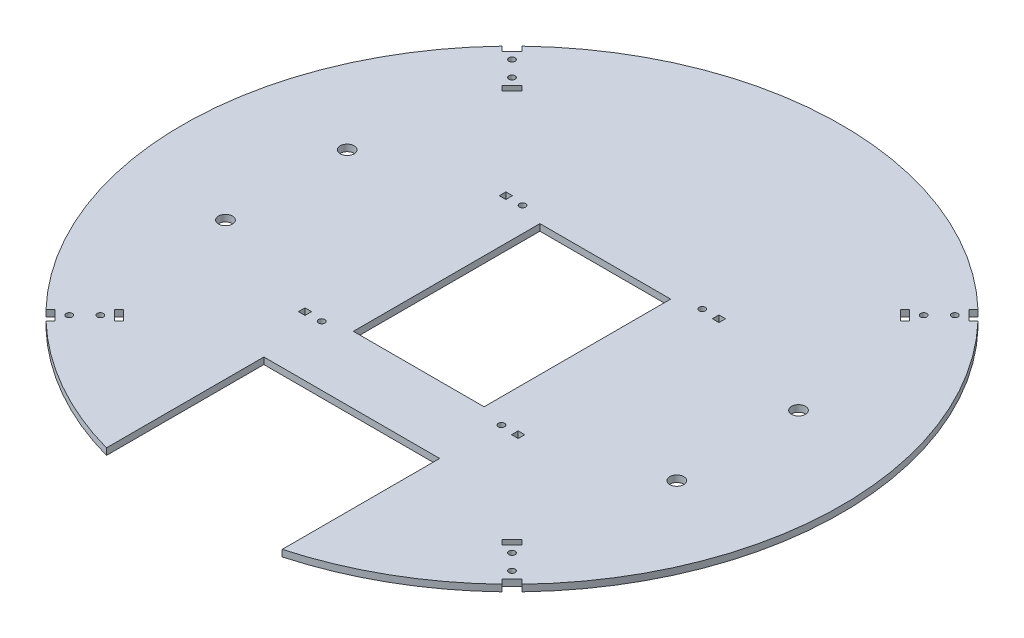
SolidWorks part; units mm, degrees
material "Acrylic (Medium-high impact)"
ref_plane "Front Plane" through (0, 0, 0) normal (0, 0, 1) x (1, 0, 0)
ref_plane "Top Plane" through (0, 0, 0) normal (0, 1, 0) x (1, 0, 0)
ref_plane "Right Plane" through (0, 0, 0) normal (1, 0, 0) x (0, 0, -1)
sketch "Sketch1" plane through (0, 0, 0) normal (0, 1, 0) x (1, 0, 0)
  line L0 (-29.75, -42.45) -> (-29.75, 42.45)
  line L1 (-31.75, -44.45) -> (31.75, -44.45) construction
  line L2 (-31.75, -44.45) -> (-31.75, 44.45) construction
  line L3 (-31.75, 44.45) -> (31.75, 44.45) construction
  line L4 (31.75, -44.45) -> (31.75, 44.45) construction
  line L5 (-31.75, -44.45) -> (31.75, 44.45) construction
  line L6 (-31.75, 44.45) -> (31.75, -44.45) construction
  line L7 (-29.75, 42.45) -> (29.75, 42.45)
  line L8 (29.75, -42.45) -> (29.75, 42.45)
  line L9 (-29.75, -42.45) -> (29.75, -42.45)
  circle A0 centre (0, 0) radius 150
  point P0 (0, 0)
  dimension "D3" = 300
  dimension "D1" = 63.5
  dimension "D2" = 88.9
  dimension "D4" = 2
extrude "Boss-Extrude1" add sketch "Sketch1" along normal blind 3
sketch "Sketch3" plane through (0, 3, 0) normal (0, 1, 0) x (1, 0, 0)
  line L0 (-42.4, 47.2) -> (-39.4, 44.2) construction
  line L1 (42.4, 47.2) -> (39.4, 44.2) construction
  line L2 (0, 0) -> (25.2091, 0) construction
  line L7 (-50, 44.2) -> (-47, 44.2)
  line L8 (-47, 44.2) -> (-47, 47.2)
  line L9 (-47, 47.2) -> (-50, 47.2)
  line L10 (-50, 47.2) -> (-50, 44.2)
  line L11 (-50, 44.2) -> (-47, 44.2)
  line L12 (-47, 44.2) -> (-47, 47.2)
  line L13 (-47, 47.2) -> (-50, 47.2)
  line L14 (-50, 47.2) -> (-50, 44.2)
  line L15 (47, 44.2) -> (50, 44.2)
  line L16 (50, 44.2) -> (50, 47.2)
  line L17 (50, 47.2) -> (47, 47.2)
  line L18 (47, 47.2) -> (47, 44.2)
  line L19 (47, 44.2) -> (50, 44.2)
  line L20 (50, 44.2) -> (50, 47.2)
  line L21 (50, 47.2) -> (47, 47.2)
  line L22 (47, 47.2) -> (47, 44.2)
  line L23 (47, -47.2) -> (50, -47.2) construction
  line L24 (50, -47.2) -> (50, -44.2) construction
  line L25 (50, -44.2) -> (47, -44.2) construction
  line L26 (47, -44.2) -> (47, -47.2) construction
  line L31 (-50, -47.2) -> (-47, -47.2) construction
  line L32 (-47, -47.2) -> (-47, -44.2) construction
  line L33 (-47, -44.2) -> (-50, -44.2) construction
  line L34 (-50, -44.2) -> (-50, -47.2) construction
  line L51 (47, -47.2) -> (50, -47.2)
  line L52 (50, -47.2) -> (50, -44.2)
  line L53 (50, -44.2) -> (47, -44.2)
  line L54 (47, -44.2) -> (47, -47.2)
  line L55 (-50, -47.2) -> (-47, -47.2)
  line L56 (-47, -47.2) -> (-47, -44.2)
  line L57 (-47, -44.2) -> (-50, -44.2)
  line L58 (-50, -44.2) -> (-50, -47.2)
  line L59 (0, 0) -> (0, -93.4335) construction
  circle A0 centre (-40.9, 45.7) radius 1.4224
  circle A1 centre (40.9, 45.7) radius 1.4224
  circle A2 centre (40.9, -45.7) radius 1.4224
  circle A3 centre (-40.9, -45.7) radius 1.4224
  circle A4 centre (-102.7, 27.7) radius 3.175
  circle A5 centre (-102.7, -27.7) radius 3.175
  circle A6 centre (102.7, 27.7) radius 3.175
  circle A7 centre (102.7, -27.7) radius 3.175
  dimension "D1" = 2.8448
  dimension "D4" = 6.35
  dimension "D2" = 0
  dimension "D3" = 0
extrude "Cut-Extrude1" cut sketch "Sketch3" against normal blind 10
sketch "Sketch4" plane through (0, 3, 0) normal (0, 1, 0) x (1, 0, 0)
  line L1 (-52.6396, -60.6627) -> (52.6396, -60.6627)
  line L2 (-52.6396, -60.6627) -> (-52.6396, 60.6627)
  line L3 (-52.6396, 60.6627) -> (52.6396, 60.6627)
  line L4 (52.6396, -60.6627) -> (52.6396, 60.6627)
  line L5 (-52.6396, -60.6627) -> (52.6396, 60.6627) construction
  line L6 (-52.6396, 60.6627) -> (52.6396, -60.6627) construction
  line L7 (-176.3133, 139.7199) -> (176.3133, 139.7199)
  line L8 (-176.3133, 139.7199) -> (-176.3133, -139.7199)
  line L9 (-176.3133, -139.7199) -> (176.3133, -139.7199)
  line L10 (176.3133, 139.7199) -> (176.3133, -139.7199)
  line L11 (-176.3133, 139.7199) -> (176.3133, -139.7199) construction
  line L12 (-176.3133, -139.7199) -> (176.3133, 139.7199) construction
  point P0 (0, 0)
  point P6 (0, 0)
extrude "Cut-Extrude2" [suppressed] cut sketch "Sketch4" against normal blind 10
sketch "Sketch6" plane through (0, 3, 0) normal (0, 1, 0) x (1, 0, 0)
  line L0 (-29.75, -42.45) -> (29.75, -42.45) construction
  line L1 (-40, -72.93) -> (40, -72.93)
  line L2 (-40, -72.93) -> (-40, -161.3295)
  line L3 (-40, -161.3295) -> (40, -161.3295)
  line L4 (40, -72.93) -> (40, -161.3295)
  line L5 (-40, -72.93) -> (40, -161.3295) construction
  line L6 (-40, -161.3295) -> (40, -72.93) construction
  point P0 (0, -117.1298)
  point P5 (0, 0)
  dimension "D1" = 30.48
  dimension "D2" = 80
extrude "Cut-Extrude3" cut sketch "Sketch6" against normal blind 3
sketch "Sketch7" plane through (0, 3, 0) normal (0, 1, 0) x (1, 0, 0)
  line L0 (0, 0) -> (0, 150) construction
  line L1 (0, 0) -> (-106.066, 106.066) construction
  line L2 (0, 0) -> (106.066, 106.066) construction
  line L3 (0, 0) -> (106.066, -106.066)
  line L4 (0, 0) -> (-106.066, -106.066) construction
  circle A0 centre (0, 0) radius 150 construction
  point P13 (0, 0)
  dimension "D1" = 45
  dimension "D2" = 4
ref_axis "Axis1" through (0, 3, 0) along (0, -1, 0)
ref_plane "Plane1" through (0, 0, 0) normal (0.7071, 0, 0.7071) x (0, -1, 0)
sketch "Sketch8" plane through (0, 0, 0) normal (0, -1, 0) x (1, 0, 0)
  line L0 (99.5234, 104.0136) -> (102.002, 97.5119) construction
  line L1 (92.4524, 96.9425) -> (94.9309, 90.4408) construction
  line L2 (103.821, 108.3111) -> (108.3111, 103.821) construction
  line L3 (106.1898, 101.6996) -> (108.3111, 103.821) construction
  line L4 (101.6996, 106.1898) -> (103.821, 108.3111) construction
  line L5 (101.6996, 106.1898) -> (106.1898, 101.6996) construction
  line L6 (90.6334, 86.1433) -> (92.7547, 88.2646)
  line L7 (92.7547, 88.2646) -> (88.2646, 92.7547)
  line L8 (88.2646, 92.7547) -> (86.1433, 90.6334)
  line L9 (86.1433, 90.6334) -> (90.6334, 86.1433)
  line L10 (90.6334, 86.1433) -> (92.7547, 88.2646)
  line L11 (92.7547, 88.2646) -> (88.2646, 92.7547)
  line L12 (88.2646, 92.7547) -> (86.1433, 90.6334)
  line L13 (86.1433, 90.6334) -> (90.6334, 86.1433)
  line L14 (103.821, 108.3111) -> (108.3111, 103.821)
  line L15 (106.1898, 101.6996) -> (108.3111, 103.821)
  line L16 (101.6996, 106.1898) -> (103.821, 108.3111)
  line L17 (101.6996, 106.1898) -> (106.1898, 101.6996)
  line L18 (86.1433, -90.6334) -> (88.2646, -92.7547)
  line L19 (88.2646, -92.7547) -> (92.7547, -88.2646)
  line L20 (92.7547, -88.2646) -> (90.6334, -86.1433)
  line L21 (90.6334, -86.1433) -> (86.1433, -90.6334)
  line L22 (108.3111, -103.821) -> (103.821, -108.3111)
  line L23 (101.6996, -106.1898) -> (103.821, -108.3111)
  line L24 (106.1898, -101.6996) -> (108.3111, -103.821)
  line L25 (106.1898, -101.6996) -> (101.6996, -106.1898)
  line L26 (104.0136, -99.5234) -> (97.5119, -102.002) construction
  line L27 (96.9425, -92.4524) -> (90.4408, -94.9309) construction
  line L28 (-90.6334, -86.1433) -> (-92.7547, -88.2646)
  line L29 (-92.7547, -88.2646) -> (-88.2646, -92.7547)
  line L30 (-88.2646, -92.7547) -> (-86.1433, -90.6334)
  line L31 (-86.1433, -90.6334) -> (-90.6334, -86.1433)
  line L32 (-103.821, -108.3111) -> (-108.3111, -103.821)
  line L33 (-106.1898, -101.6996) -> (-108.3111, -103.821)
  line L34 (-101.6996, -106.1898) -> (-103.821, -108.3111)
  line L35 (-101.6996, -106.1898) -> (-106.1898, -101.6996)
  line L36 (-99.5234, -104.0136) -> (-102.002, -97.5119) construction
  line L37 (-92.4524, -96.9425) -> (-94.9309, -90.4408) construction
  line L38 (-86.1433, 90.6334) -> (-88.2646, 92.7547)
  line L39 (-88.2646, 92.7547) -> (-92.7547, 88.2646)
  line L40 (-92.7547, 88.2646) -> (-90.6334, 86.1433)
  line L41 (-90.6334, 86.1433) -> (-86.1433, 90.6334)
  line L42 (-108.3111, 103.821) -> (-103.821, 108.3111)
  line L43 (-101.6996, 106.1898) -> (-103.821, 108.3111)
  line L44 (-106.1898, 101.6996) -> (-108.3111, 103.821)
  line L45 (-106.1898, 101.6996) -> (-101.6996, 106.1898)
  line L46 (-104.0136, 99.5234) -> (-97.5119, 102.002) construction
  line L47 (-96.9425, 92.4524) -> (-90.4408, 94.9309) construction
  circle A0 centre (100.7627, 100.7627) radius 1.4224
  circle A1 centre (93.6916, 93.6916) radius 1.4224
  circle A2 centre (100.7627, -100.7627) radius 1.4224
  circle A3 centre (93.6916, -93.6916) radius 1.4224
  circle A4 centre (-100.7627, -100.7627) radius 1.4224
  circle A5 centre (-93.6916, -93.6916) radius 1.4224
  circle A6 centre (-100.7627, 100.7627) radius 1.4224
  circle A7 centre (-93.6916, 93.6916) radius 1.4224
  point P19 (0, 0)
  point P71 (0, 0)
  dimension "D1" = 2.8448
  dimension "D2" = 0
  dimension "D3" = 4
ref_plane "Plane2" through (-90.6334, 0, 86.1433) normal (0, -1, 0) x (-1, 0, 0)
extrude "Cut-Extrude5" cut sketch "Sketch8" against normal blind 3
